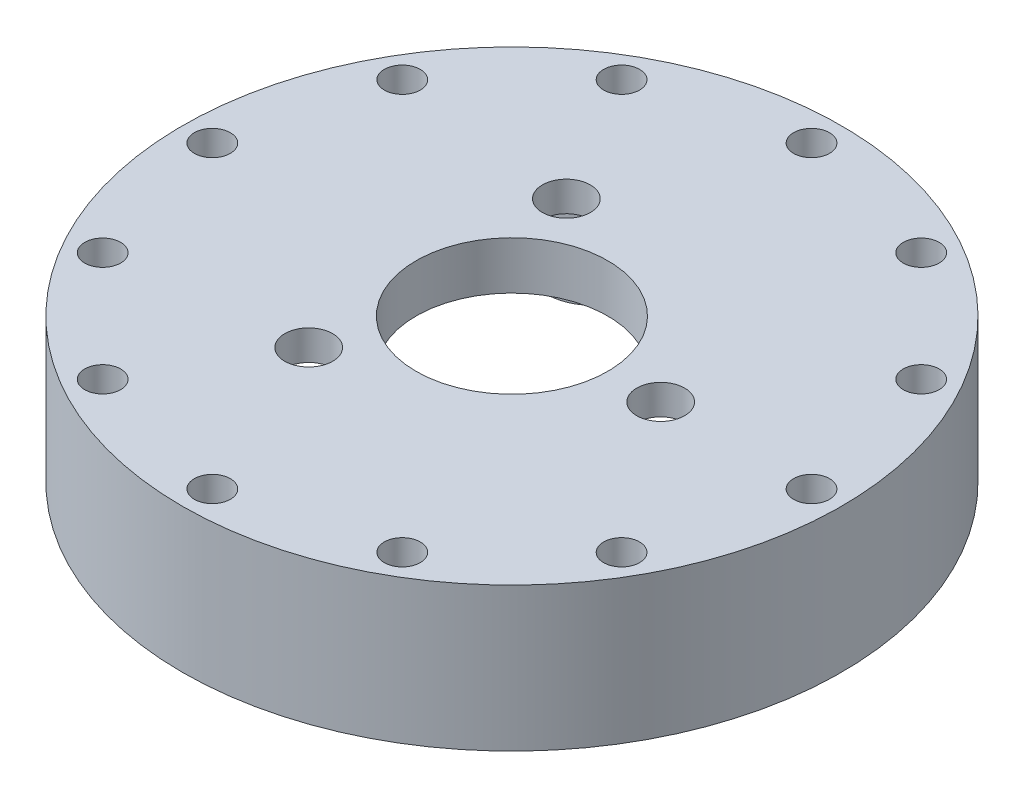
SolidWorks part; units mm, degrees
ref_plane "Front Plane" through (0, 0, 0) normal (0, 0, 1) x (1, 0, 0)
ref_plane "Top Plane" through (0, 0, 0) normal (0, 1, 0) x (1, 0, 0)
ref_plane "Right Plane" through (0, 0, 0) normal (1, 0, 0) x (0, 0, -1)
sketch "Sketch1" plane through (0, 0, 0) normal (0, 1, 0) x (1, 0, 0)
  line L0 (0, 22.5) -> (0, 0) construction
  line L1 (0, 0) -> (12.1644, 18.9282) construction
  line L2 (0, 0) -> (-12.1644, 18.9282) construction
  line L3 (-20.4667, 9.3468) -> (0, 0) construction
  line L4 (0, 0) -> (-22.271, -3.2021) construction
  circle A0 centre (0, 0) radius 22.5
  circle A1 centre (0, 0) radius 27.5
  circle A2 centre (0, 22.5) radius 3.925
  circle A3 centre (12.1644, 18.9282) radius 3.925
  circle A4 centre (20.4667, 9.3468) radius 3.925
  circle A5 centre (22.271, -3.2021) radius 3.925
  circle A6 centre (17.0044, -14.7344) radius 3.925
  circle A7 centre (6.339, -21.5886) radius 3.925
  circle A8 centre (-6.339, -21.5886) radius 3.925
  circle A9 centre (-17.0044, -14.7344) radius 3.925
  circle A10 centre (-22.271, -3.2021) radius 3.925
  circle A11 centre (-20.4667, 9.3468) radius 3.925
  circle A12 centre (-12.1644, 18.9282) radius 3.925
  point P27 (0, 0)
  dimension "D1" = 45
  dimension "D2" = 55
  dimension "D3" = 7.85
  dimension "D4" = 11
extrude "Boss-Extrude2" add sketch "Sketch1" along normal blind 8 contours A1 A12 A0 A2 A3 A4 A5 A6 A7 A8 A9 A10 A11 | A0 A11 | A0 A11 | A0 A12 | A0 A12 | A0 A2 | A0 A2 | A0 A3 | A0 A3 | A0 A4 | A0 A4 | A0 A5 | A0 A5 | A0 A6 | A0 A6 | A0 A7 | A0 A7 | A0 A8 | A0 A8 | A0 A9 | A0 A9 | A0 A10 | A0 A10 | A12 region at (20.5626, 0, 2.9565) region at (23.8573, 0, 3.4302) region at (18.8967, 0, -8.6299) region at (21.9245, 0, -10.0126) region at (18.2156, 0, 15.7839) region at (15.7, 0, 13.6041) region at (11.2313, 0, -17.4762) region at (13.0309, 0, -20.2764) region at (6.7905, 0, 23.1263) region at (5.8527, 0, 19.9326) region at (0, 0, -20.774) region at (0, 0, -24.1026) region at (-6.7905, 0, 23.1263) region at (-5.8527, 0, 19.9326) region at (-11.2313, 0, -17.4762) region at (-13.0309, 0, -20.2764) region at (-18.2156, 0, 15.7839) region at (-15.7, 0, 13.6041) region at (-18.8967, 0, -8.6299) region at (-21.9245, 0, -10.0126) region at (-23.8573, 0, 3.4302) region at (-20.5626, 0, 2.9565) region at (-26.7222, 0, 0)
sketch "Sketch2" plane through (0, 8, 0) normal (0, 1, 0) x (1, 0, 0)
  line L1 (12.413, 0) -> (-6.2065, 10.75) construction
  line L2 (-6.2065, 10.75) -> (-6.2065, -10.75) construction
  line L3 (-6.2065, -10.75) -> (12.413, 0) construction
  circle A0 centre (0, 0) radius 27.5
  circle A1 centre (0, 0) radius 8
  circle A2 centre (0, 0) radius 6.2065 construction
  circle A3 centre (-6.2065, 10.75) radius 2
  circle A4 centre (12.413, 0) radius 2
  circle A5 centre (-6.2065, -10.75) radius 2
  point P16 (0, 0)
  dimension "D1" = 16
  dimension "D2" = 55
  dimension "D4" = 4
  dimension "D3" = 21.5
  dimension "D5" = 3
extrude "Boss-Extrude3" add sketch "Sketch2" along normal blind 4
fillet "Fillet2" radius 1 22 edges at (19.3062, 4, 11.5552) (9.9942, 4, 20.1585) (2.4909, 4, 22.3617) (14.1851, 4, 17.4652) (-2.4909, 4, 22.3617) (-9.9942, 4, 20.1585) (-14.1851, 4, 17.4652) (-19.3062, 4, 11.5552) (-21.3757, 4, 7.0236) (-22.4886, 4, -0.7169) (-21.7796, 4, -5.6479) (-18.531, 4, -12.7613) (-15.2687, 4, -16.5263) (-8.69, 4, -20.7541) (-3.91, 4, -22.1577) (3.91, 4, -22.1577) (8.69, 4, -20.7541) (15.2687, 4, -16.5263) (18.531, 4, -12.7613) (21.7796, 4, -5.6479) (22.4886, 4, -0.7169) (21.3757, 4, 7.0236)
sketch "Sketch8" plane through (0, 0, 0) normal (0, -1, 0) x (1, 0, 0)
  circle A0 centre (0, 0) radius 25 construction
  circle A1 centre (0, -25) radius 1.5
  circle A2 centre (-12.5, -21.6506) radius 1.5
  circle A3 centre (-21.6506, -12.5) radius 1.5
  circle A4 centre (-25, 0) radius 1.5
  circle A5 centre (-21.6506, 12.5) radius 1.5
  circle A6 centre (-12.5, 21.6506) radius 1.5
  circle A7 centre (0, 25) radius 1.5
  circle A8 centre (12.5, 21.6506) radius 1.5
  circle A9 centre (21.6506, 12.5) radius 1.5
  circle A10 centre (25, 0) radius 1.5
  circle A11 centre (21.6506, -12.5) radius 1.5
  circle A12 centre (12.5, -21.6506) radius 1.5
  point P30 (0, 0)
  dimension "D1" = 50
  dimension "D2" = 3
  dimension "D3" = 12
extrude "Cut-Extrude1" cut sketch "Sketch8" against normal through all
sketch "Sketch9" plane through (0, 8, 0) normal (0, -1, 0) x (1, 0, 0)
  circle A0 centre (0, 0) radius 12.413 construction
  circle A1 centre (12.413, 0) radius 4.25
  circle A2 centre (-6.2065, -10.75) radius 4.25
  circle A3 centre (-6.2065, 10.75) radius 4.25
  point P13 (0, 0)
  dimension "D1" = 8.5
  dimension "D2" = 3
extrude "Cut-Extrude2" cut sketch "Sketch9" against normal blind 1.5
